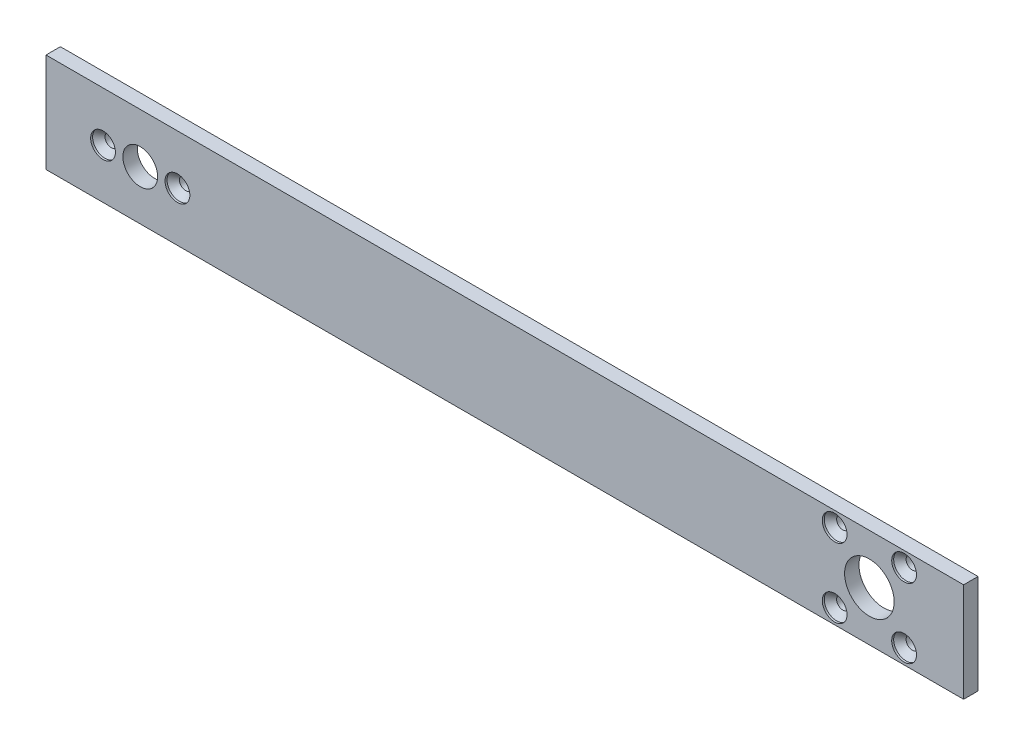
SolidWorks part; units mm, degrees
ref_plane "Front Plane" through (0, 0, 0) normal (0, 0, 1) x (1, 0, 0)
ref_plane "Top Plane" through (0, 0, 0) normal (0, 1, 0) x (1, 0, 0)
ref_plane "Right Plane" through (0, 0, 0) normal (1, 0, 0) x (0, 0, -1)
sketch "Sketch1" plane through (0, 0, 0) normal (0, 0, 1) x (1, 0, 0)
  line L1 (-92.5, 10) -> (92.5, 10)
  line L2 (-92.5, 10) -> (-92.5, -10)
  line L3 (-92.5, -10) -> (92.5, -10)
  line L4 (92.5, 10) -> (92.5, -10)
  line L5 (-92.5, 10) -> (92.5, -10) construction
  line L6 (-92.5, -10) -> (92.5, 10) construction
  point P0 (0, 0)
  dimension "D1" = 20
  dimension "D2" = 185
extrude "Base shape" add sketch "Sketch1" against normal blind 2.9
sketch "Sketch2" plane through (0, 0, 0) normal (0, 0, 1) x (1, 0, 0)
  line L0 (-83.5, 10) -> (-83.5, -10) construction
  line L1 (92.5, 10) -> (-92.5, 10) construction
  line L2 (-92.5, -10) -> (92.5, -10) construction
  line L3 (-92.5, 10) -> (-92.5, -10) construction
  line L4 (-92.5, 0) -> (92.5, 0) construction
  line L5 (92.5, -10) -> (92.5, 10) construction
  line L6 (-73.5, 10) -> (-73.5, -10) construction
  line L7 (0, 10) -> (0, -10) construction
  line L8 (73.5, 5) -> (92.5, 5) construction
  line L9 (-73.5, 3.5) -> (-92.5, 3.5) construction
  line L11 (80.5, -7) -> (66.5, -7)
  line L12 (80.5, -7) -> (80.5, 7)
  line L13 (80.5, 7) -> (66.5, 7)
  line L14 (66.5, -7) -> (66.5, 7)
  line L15 (80.5, -7) -> (66.5, 7) construction
  line L16 (80.5, 7) -> (66.5, -7) construction
  circle A0 centre (-73.5, 0) radius 10
  circle A1 centre (-81, 0) radius 1.25
  circle A2 centre (-66, 0) radius 1.25
  circle A3 centre (-73.5, 0) radius 3.5
  circle A4 centre (73.5, 0) radius 5
  circle A5 centre (66.5, 7) radius 1.25
  circle A6 centre (80.5, 7) radius 1.25
  circle A7 centre (80.5, -7) radius 1.25
  circle A8 centre (66.5, -7) radius 1.25
  dimension "D2" = 20
  dimension "D3" = 2.5
  dimension "D4" = 15
  dimension "D5" = 7
  dimension "D6" = 10
  dimension "D8" = 2.5
  dimension "D1" = 147
  dimension "D7" = 14
extrude "Motor cutouts" cut sketch "Sketch2" against normal up to next contours A5 | A6 | A7 | A8 | A1 | A2 | A3 | A4
hole_wizard "Countersunk chamfers" positions "Sketch3" profile "Sketch4" countersink size "M2.5" standard "ANSI Metric" end condition through all
sketch "Sketch3" plane through (0, 0, 0) normal (0, 0, 1) x (1, 0, 0)
  point P0 (-81, 0)
  point P3 (-66, 0)
  point P7 (66.5, 7)
  point P10 (80.5, 7)
  point P13 (66.5, -7)
  point P16 (80.5, -7)
sketch "Sketch4" plane through (-81, 0, 0) normal (1, 0, 0) x (0, -1, 0)
  line L0 (0, 0) -> (0, 2.9)
  line L1 (0, 2.9) -> (1.25, 2.9)
  line L2 (1.25, 2.9) -> (1.25, 1.65)
  line L3 (1.25, 1.65) -> (2.5, 0.4)
  line L4 (2.5, 0.4) -> (2.5, 0)
  line L6 (2.5, 0) -> (0, 0)
  line L7 (-1.25, 1.65) -> (-2.5, 0.4) construction
  line L11 (0, -6.35) -> (0, 107.95) construction
  dimension "Thru Hole Dia." = 2.5
  dimension "Thru Hole Depth" = 2.9
  dimension "C'Sink Dia." = 5
  dimension "C'Sink Angle" = 90
  dimension "Head Clearance" = 0.4
sketch "Sketch5" plane through (0, 0, -2.9) normal (0, 0, -1) x (-1, 0, 0)
  line L0 (0, 10) -> (0, -10) construction
  line L3 (-92.5, 10) -> (92.5, 10) construction
  line L4 (92.5, -10) -> (-92.5, -10) construction
  line L5 (-60, -7) -> (60, -7) construction
  line L6 (-60, -6) -> (60, -6)
  line L7 (-60, -8) -> (60, -8)
  arc A0 (-60, -6) -> (-60, -8) centre (-60, -7) ccw
  arc A1 (60, -8) -> (60, -6) centre (60, -7) ccw
  point P8 (0, -7)
  dimension "D1" = 120
  dimension "D2" = 2
  dimension "D3" = 2
extrude "PCB slot" cut sketch "Sketch5" against normal blind 0.775
